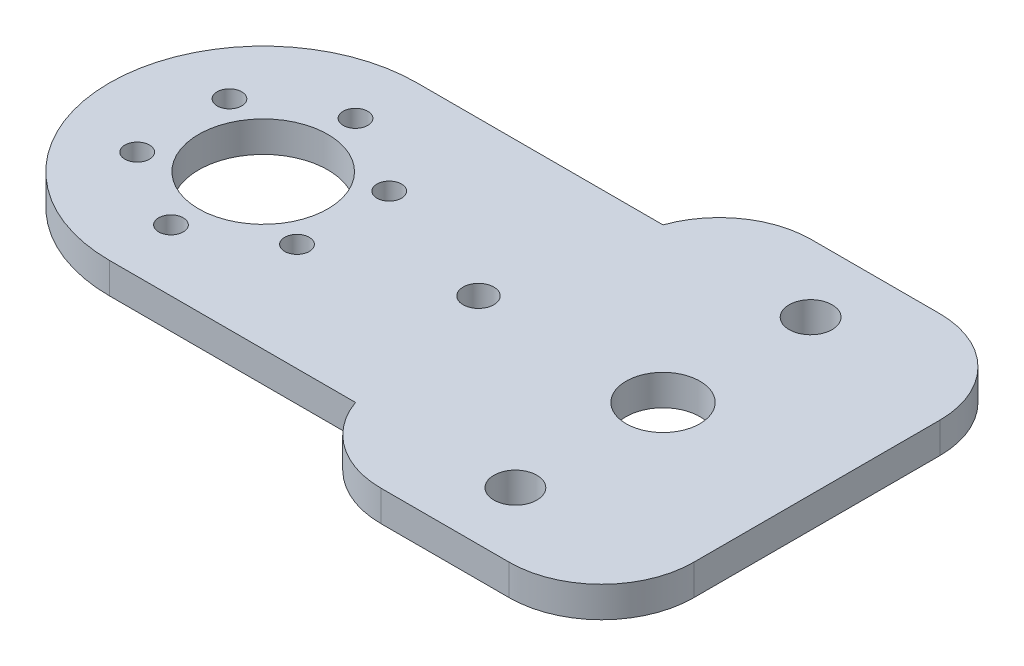
SolidWorks part; units mm, degrees
material "Acrylic (Medium-high impact)"
ref_plane "Front Plane" through (0, 0, 0) normal (0, 0, 1) x (1, 0, 0)
ref_plane "Top Plane" through (0, 0, 0) normal (0, 1, 0) x (1, 0, 0)
ref_plane "Right Plane" through (0, 0, 0) normal (1, 0, 0) x (0, 0, -1)
sketch "Sketch1" plane through (0, 0, 0) normal (0, 1, 0) x (1, 0, 0)
  line L0 (0, 0) -> (65, 0) construction
  line L3 (0, 0) -> (0, 25) construction
  line L4 (0, 0) -> (65, 0) construction
  line L5 (40, -35) -> (90, -35)
  line L6 (40, -35) -> (40, 35)
  line L8 (40, 35) -> (90, 35)
  line L9 (90, -35) -> (90, 35)
  line L10 (0, 25) -> (65, 25)
  line L11 (0, -25) -> (65, -25)
  circle A2 centre (0, 0) radius 10.5
  circle A3 centre (0, 15) radius 2
  circle A4 centre (12.9904, 7.5) radius 2
  circle A5 centre (12.9904, -7.5) radius 2
  circle A6 centre (0, -15) radius 2
  circle A7 centre (-12.9904, -7.5) radius 2
  circle A8 centre (-12.9904, 7.5) radius 2
  circle A9 centre (65, 0) radius 6
  arc A13 (0, 25) -> (0, -25) centre (0, 0) ccw
  circle A14 centre (65, 24) radius 3.5
  circle A15 centre (65, -24) radius 3.5
  arc A16 (65, -25) -> (65, 25) centre (65, 0) ccw
  circle A17 centre (35, 0) radius 2.5
  point P5 (32.5, 0)
  point P28 (0, 0)
  dimension "D2" = 21
  dimension "D3" = 25
  dimension "D4" = 4
  dimension "D5" = 15
  dimension "D9" = 12
  dimension "D12" = 35
  dimension "D14" = 35
  dimension "D15" = 65
  dimension "D18" = 7
  dimension "D11" = 50
  dimension "D13" = 5
  dimension "D7" = 15
  dimension "D8" = 15
  dimension "D10" = 70
  dimension "D17" = 24
  dimension "D6" = 6
extrude "Boss-Extrude1" add sketch "Sketch1" along normal blind 5 contours L10 A13 L11 L6 A2 A3 A4 A5 A6 A7 A8 | A15 A16 A14 L10 L6 L11 A9 | A16 A15 L11 L6 L5 L9 | A16 L9 L8 L6 L10 A14 region at (69.1889, 0, 27.7967) region at (11.3748, 0, 0) region at (40.7071, 0, 0) region at (69.1889, 0, -27.7967)
fillet "Fillet2" radius 15 4 edges at (40, 2.5, -35) (90, 2.5, 35) (90, 2.5, -35) (40, 2.5, 35)
